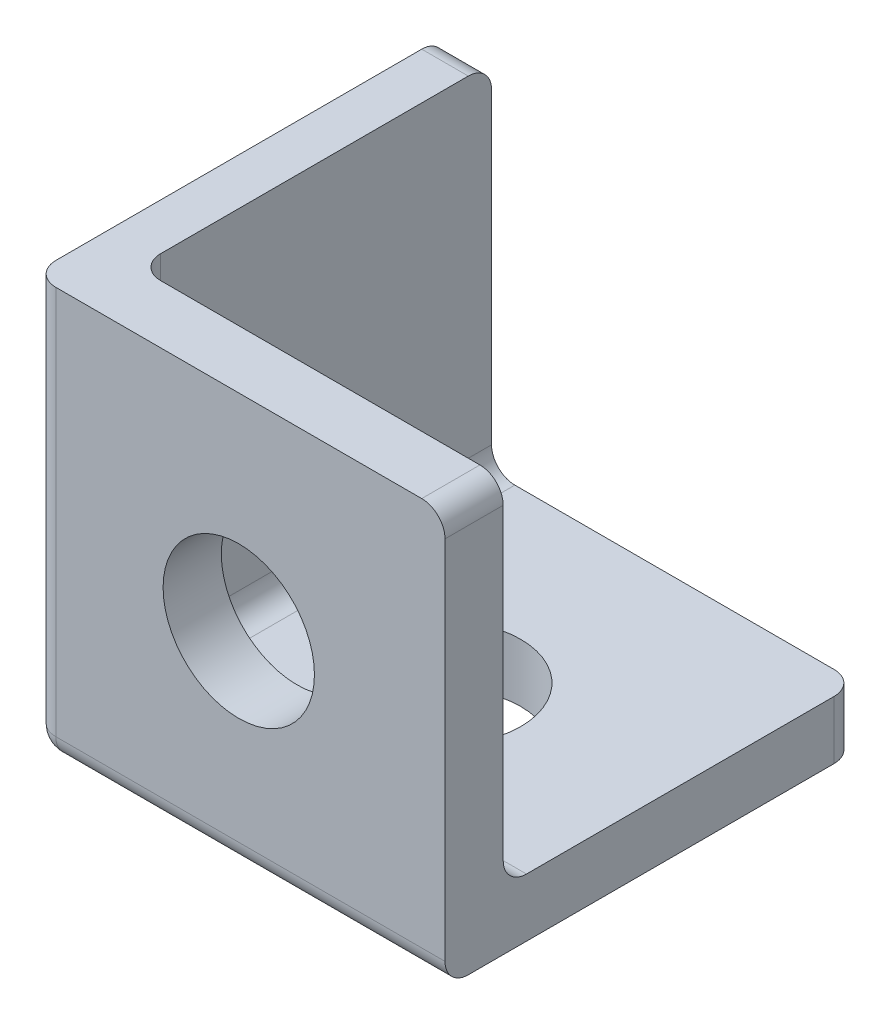
SolidWorks part; units mm, degrees
ref_plane "Front Plane" through (0, 0, 0) normal (0, 0, 1) x (1, 0, 0)
ref_plane "Top Plane" through (0, 0, 0) normal (0, 1, 0) x (1, 0, 0)
ref_plane "Right Plane" through (0, 0, 0) normal (1, 0, 0) x (0, 0, -1)
sketch "Sketch2" plane through (0, 0, 0) normal (1, 0, 0) x (0, 0, -1)
  line L0 (45, 0) -> (0, 0)
  line L1 (0, 0) -> (0, 45)
  line L2 (0, 45) -> (6.35, 45)
  line L4 (45, 6.35) -> (45, 0)
  line L5 (45, 6.35) -> (6.35, 6.35)
  line L6 (6.35, 6.35) -> (6.35, 45)
  line L7 (45, 6.35) -> (45, 45)
  line L8 (45, 45) -> (6.35, 45)
  point P9 (0, 0)
  point P10 (0, 0)
  point P11 (0, 0)
  dimension "D1" = 45
  dimension "D2" = 6.35
extrude "Boss-Extrude1" add sketch "Sketch2" along normal blind 45 contours L5 L6 L2 L1 L0 L4 region at (0, 0.6364, -22.5)
sketch "Sketch3" plane through (0, 6.35, 0) normal (0, 1, 0) x (1, 0, 0)
  line L0 (45, 45) -> (45, 0) construction
  line L2 (45, 45) -> (0, 45) construction
  circle A0 centre (22.5, 22.5) radius 8.255
  point P4 (45, 22.5)
  point P9 (22.5, 45)
  dimension "D1" = 16.51
extrude "Cut-Extrude1" cut sketch "Sketch3" against normal through all
sketch "Sketch4" plane through (0, 0, -6.35) normal (0, 0, -1) x (-1, 0, 0)
  line L0 (-45, 45) -> (0, 45) construction
  line L1 (-45, 0) -> (-45, 45) construction
  line L2 (-14.245, 6.35) -> (-30.755, 6.35) construction
  line L3 (-14.245, 6.35) -> (-30.755, 6.35) construction
  circle A0 centre (-22.5, 22.5) radius 8.255
  point P4 (-22.5, 45)
  point P7 (-45, 22.5)
  point P10 (-30.755, 22.5)
  point P11 (0, 0)
extrude "Boss-Extrude2" add sketch "Sketch2<3>" along normal blind 5.08 contours L6 L5 region at (0, 25.675, -25.675)
sketch "Sketch2<3>" plane through (0, 0, 0) normal (1, 0, 0) x (0, 0, -1) same geometry as "Sketch2"
extrude "Cut-Extrude2" cut sketch "Sketch4" against normal through all
fillet "Fillet1" radius 2.54 9 edges at (45, 3.175, -45) (45, 45, -3.175) (25.04, 6.35, -6.35) (5.08, 6.35, -25.675) (5.08, 25.675, -6.35) (2.54, 45, -45) (0, 22.5, 0) (22.5, 0, 0) (0, 0, -22.5)
equation "\"D1@Sketch2\"=45mm"
